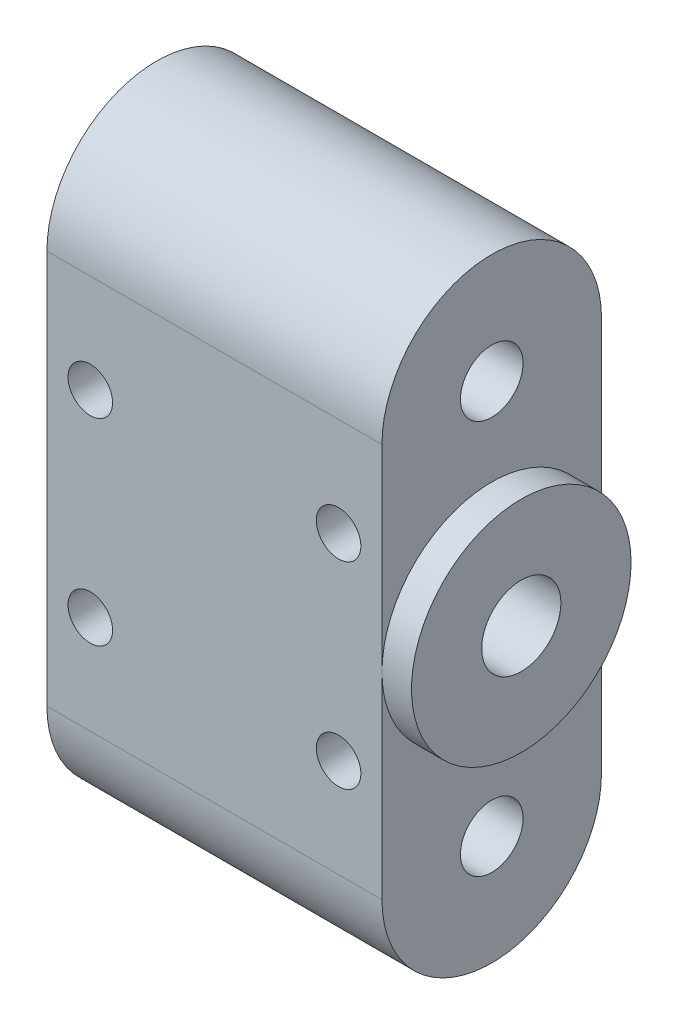
SolidWorks part; units mm, degrees
material "PET"
ref_plane "Front" through (0, 0, 0) normal (0, 0, 1) x (1, 0, 0)
ref_plane "Top" through (0, 0, 0) normal (0, 1, 0) x (1, 0, 0)
ref_plane "Right" through (0, 0, 0) normal (1, 0, 0) x (0, 0, -1)
sketch "Sketch1" plane through (0, 0, 0) normal (1, 0, 0) x (0, 0, -1)
  line L0 (0, 12.7) -> (0, -12.7) construction
  line L1 (7.0739, 12.7) -> (7.0739, -12.7)
  line L2 (-7.0739, 12.7) -> (-7.0739, -12.7)
  arc A0 (7.0739, 12.7) -> (-7.0739, 12.7) centre (0, 12.7) ccw
  arc A1 (-7.0739, -12.7) -> (7.0739, -12.7) centre (0, -12.7) ccw
  point P2 (0, 0)
  dimension "D1" = 14.1478
  dimension "D2" = 25.4
extrude "Boss-Extrude1" add sketch "Sketch1" along normal blind 21.59
sketch "Sketch8" plane through (21.59, 0, 0) normal (1, 0, 0) x (0, 0, -1)
  circle A0 centre (0, 0) radius 7.0739
  dimension "D1" = 14.1478
extrude "Boss-Extrude2" add sketch "Sketch8" along normal blind 1.905
hole_wizard "1/4-20 Tapped Hole1" positions "Sketch9" profile "Sketch10" tap size "1/4-20" standard "ANSI Inch" end condition through all
sketch "Sketch9" plane through (23.495, 0, 0) normal (1, 0, 0) x (0, 0, -1)
  point P0 (0, 0)
sketch "Sketch10" plane through (23.495, 0, 0) normal (0, 1, 0) x (0, 0, -1)
  line L0 (0, 0) -> (0, 23.495)
  line L1 (0, 23.495) -> (2.5527, 23.495)
  line L2 (2.5527, 23.495) -> (2.5527, 0)
  line L5 (2.5527, 0) -> (0, 0)
  line L11 (0, -6.35) -> (0, 107.95) construction
  dimension "Thru Tap Drill Dia." = 5.1054
  dimension "Thru Tap Drill Depth" = 23.495
cosmetic thread "Hole Thread8" parameters "D2"=6.35
hole_wizard "#10-32 Tapped Hole1" positions "Sketch4" profile "Sketch5" tap size "#10-32" standard "ANSI Inch" end condition through all
sketch "Sketch4" plane through (21.59, 0, 0) normal (1, 0, 0) x (0, 0, -1)
  point P0 (0, 12.7)
  point P2 (0, -12.7)
sketch "Sketch5" plane through (21.59, 12.7, 0) normal (0, 1, 0) x (0, 0, -1)
  line L0 (0, 0) -> (0, 21.59)
  line L1 (0, 21.59) -> (2.0193, 21.59)
  line L2 (2.0193, 21.59) -> (2.0193, 0)
  line L5 (2.0193, 0) -> (0, 0)
  line L11 (0, -6.35) -> (0, 107.95) construction
  dimension "Thru Tap Drill Dia." = 4.0386
  dimension "Thru Tap Drill Depth" = 21.59
cosmetic thread "Hole Thread2" parameters "D2"=4.826
cosmetic thread "Hole Thread3" parameters "D2"=4.826
hole_wizard "#6-40 Tapped Hole1" positions "Sketch6" profile "Sketch7" tap size "#6-40" standard "ANSI Inch" end condition through all
sketch "Sketch6" plane through (0, 0, 7.0739) normal (0, 0, 1) x (1, 0, 0)
  line L5 (2.795, 6.35) -> (2.795, -6.35) construction
  line L7 (0, 0) -> (21.59, 0) construction
  line L8 (0, 12.7) -> (0, -12.7) construction
  line L12 (2.795, 6.35) -> (18.795, 6.35) construction
  line L14 (10.795, 6.35) -> (10.795, 0) construction
  line L15 (21.59, 12.7) -> (21.59, 0) construction
  point P0 (2.795, 6.35)
  point P2 (18.795, 6.35)
  point P4 (2.795, -6.35)
  point P6 (18.795, -6.35)
  point P54 (2.795, 0)
  dimension "D1" = 16
  dimension "D2" = 12.7
cosmetic thread "Hole Thread4" parameters "D2"=3.5052
cosmetic thread "Hole Thread5" parameters "D2"=3.5052
cosmetic thread "Hole Thread6" parameters "D2"=3.5052
cosmetic thread "Hole Thread7" parameters "D2"=3.5052
sketch "Sketch7" plane through (2.795, 6.35, 7.0739) normal (1, 0, 0) x (0, -1, 0)
  line L0 (0, 0) -> (0, 14.1478)
  line L1 (0, 14.1478) -> (1.4351, 14.1478)
  line L2 (1.4351, 14.1478) -> (1.4351, 0)
  line L5 (1.4351, 0) -> (0, 0)
  line L11 (0, -6.35) -> (0, 107.95) construction
  dimension "Thru Tap Drill Dia." = 2.8702
  dimension "Thru Tap Drill Depth" = 14.1478
